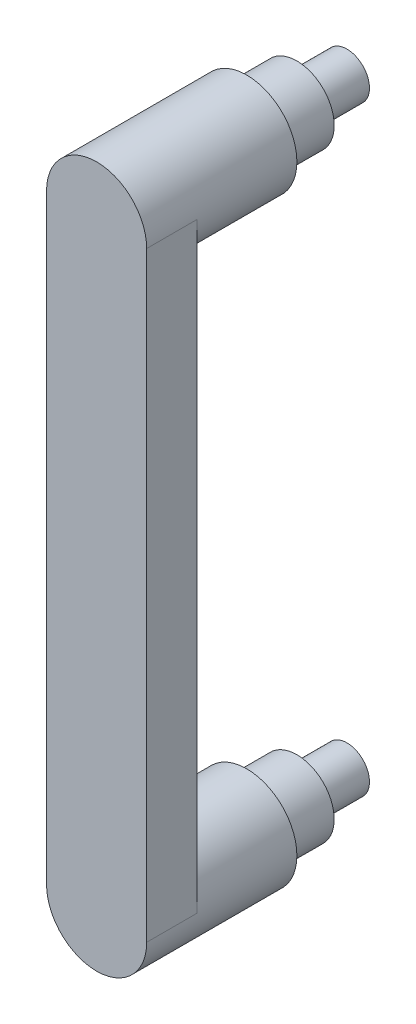
SolidWorks part; units mm, degrees
ref_plane "前视基准面" through (0, 0, 0) normal (0, 0, 1) x (1, 0, 0)
ref_plane "上视基准面" through (0, 0, 0) normal (0, 1, 0) x (1, 0, 0)
ref_plane "右视基准面" through (0, 0, 0) normal (1, 0, 0) x (0, 0, -1)
sketch "草图1" plane through (0, 0, 0) normal (0, 0, 1) x (1, 0, 0)
  circle A0 centre (0, 0) radius 1.49
  dimension "D1" = 2.98
extrude "凸台-拉伸1" add sketch "草图1" along normal blind 4
sketch "草图2" plane through (0, 0, 0) normal (0, 0, -1) x (-1, 0, 0)
  circle A0 centre (0, 0) radius 2
  dimension "D1" = 4
extrude "凸台-拉伸2" add sketch "草图2" along normal blind 4
sketch "草图3" plane through (0, 0, 4) normal (0, 0, 1) x (1, 0, 0)
  circle A0 centre (0, 0) radius 2
  dimension "D1" = 4
extrude "凸台-拉伸3" add sketch "草图3" along normal blind 4
sketch "草图4" plane through (0, 0, 0) normal (0, 1, 0) x (1, 0, 0)
  line L0 (2, 4) -> (-2, 4) construction
  line L1 (-2, 4) -> (2, 4)
  line L2 (-2, 4) -> (-2, 6)
  line L3 (-2, 6) -> (2, 6)
  line L4 (2, 4) -> (2, 6)
  dimension "D1" = 2
extrude "凸台-拉伸4" add sketch "草图4" along normal blind 12 and the other way up to surface other way up to face at (-2, 0, -4)
sketch "草图6" plane through (0, 0, 0) normal (0, 1, 0) x (1, 0, 0)
  line L1 (-2, -8) -> (2, -8)
  line L2 (-2, -8) -> (-2, -10)
  line L3 (-2, -10) -> (2, -10)
  line L4 (2, -8) -> (2, -10)
  dimension "D1" = 2
extrude "凸台-拉伸5" add sketch "草图6" along normal blind 12 and the other way up to surface other way up to face at (2, 0, 8)
ref_plane "基准面4" through (0, 12, 0) normal (0, 1, 0) x (1, 0, 0)
mirror "镜向2" about plane through (0, 12, 0) normal (0, 1, 0) of bodies 105
sketch "草图7" plane through (0, 0, 0) normal (1, 0, 0) x (0, 0, -1)
  line L5 (-10, 26) -> (6, 26) construction
  line L6 (6, -2) -> (6, 0) construction
  line L7 (-2, 26) -> (6, 26)
  line L8 (-2, 26) -> (-2, -2)
  line L9 (-2, -2) -> (6, -2)
  line L10 (6, 26) -> (6, -2)
extrude "切除-拉伸1" cut sketch "草图7" against normal blind 12 and the other way blind 12
sketch "草图8" plane through (0, 0, 2) normal (0, 0, -1) x (-1, 0, 0)
  circle A0 centre (0, 24) radius 0.9
  circle A1 centre (0, 0) radius 0.9
  dimension "D1" = 1.8
  dimension "D2" = 1.8
extrude "凸台-拉伸6" add sketch "草图8" along normal blind 2
